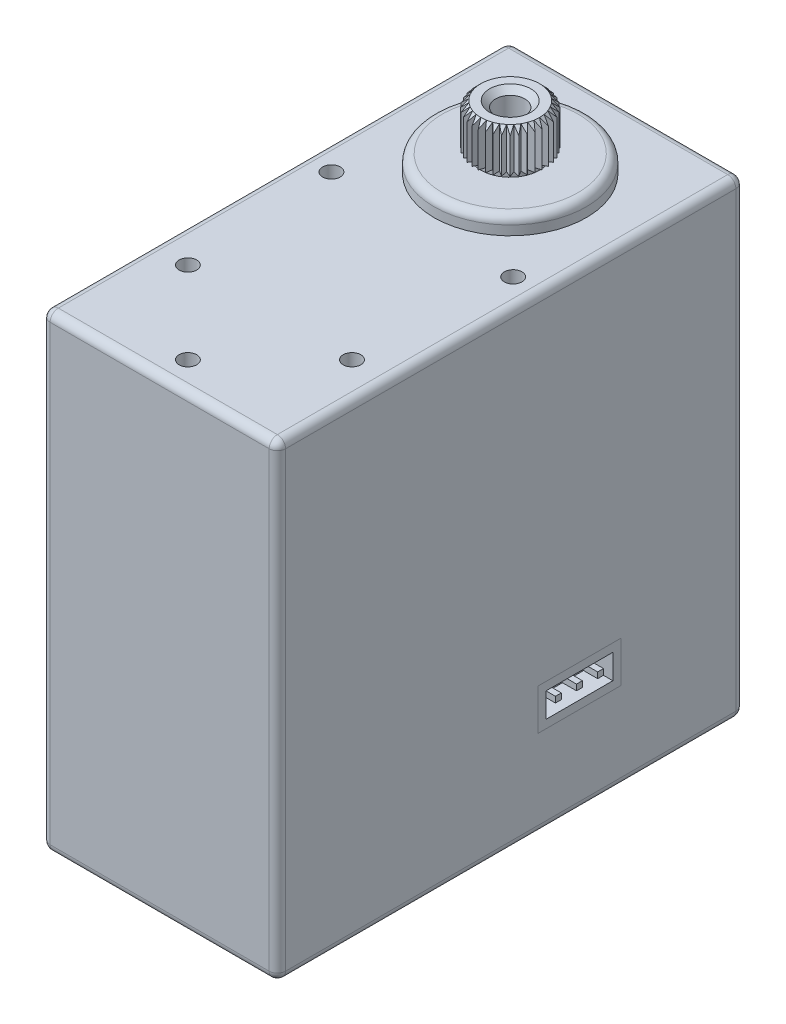
SolidWorks part; units mm, degrees
ref_plane "Alzado" through (0, 0, 0) normal (0, 0, 1) x (1, 0, 0)
ref_plane "Planta" through (0, 0, 0) normal (0, 1, 0) x (1, 0, 0)
ref_plane "Vista lateral" through (0, 0, 0) normal (1, 0, 0) x (0, 0, -1)
sketch "Croquis2" plane through (0, 0, 0) normal (0, 1, 0) x (1, 0, 0)
  line L0 (0, 0) -> (0, -27.5) construction
  line L1 (0, 7.5) -> (0, 9.91) construction
  line L2 (0, -7.5) -> (7.75, -7.5) construction
  line L3 (0, -20.5) -> (7, -20.5) construction
  line L4 (0, 0) -> (0, 7.5) construction
  line L5 (0, 7.5) -> (7.5, 7.5)
  line L6 (0, -27.5) -> (0, -29.91) construction
  line L7 (-10.045, -29.91) -> (10.045, -29.91)
  line L8 (-10.045, 9.91) -> (10.045, 9.91)
  line L9 (10.045, -29.91) -> (10.045, 9.91)
  line L10 (-10.045, -29.91) -> (-10.045, 9.91)
  circle A0 centre (0, 0) radius 3
  circle A3 centre (0, 0) radius 6.5
  circle A4 centre (7, -20.5) radius 0.75
  circle A6 centre (7.5, 7.5) radius 0.75
  circle A10 centre (0, -27.5) radius 0.75
  circle A11 centre (7.75, -7.5) radius 0.75
  circle A13 centre (-7, -20.5) radius 0.75
  circle A14 centre (-7.75, -7.5) radius 0.75
  dimension "D1" = 27.5
  dimension "D2" = 6
  dimension "D3" = 7
  dimension "D4" = 13
  dimension "D7" = 13
  dimension "D5" = 1.5
  dimension "D10" = 1.5
  dimension "D11" = 2.41
  dimension "D12" = 1.5
  dimension "D13" = 2.41
  dimension "D9" = 1.5
  dimension "D6" = 7
  dimension "D8" = 7.5
  dimension "D14" = 10.045
  dimension "D15" = 10.045
  dimension "D16" = 7.75
extrude "Saliente-Extruir1" add sketch "Croquis2" along normal blind 5.4 contours A0 region at (0, 0, 0)
extrude "Saliente-Extruir2" add sketch "Croquis2<4>" along normal blind 1.5 contours A3 region at (-6.3162, 0, 0)
sketch "Croquis2<4>" plane through (0, 0, 0) normal (0, 1, 0) x (1, 0, 0) same geometry as "Croquis2"
extrude "Saliente-Extruir3" add sketch "Croquis2<6>" against normal blind 40 separate body contours L10 L7 L9 L8 A14 A11 A10 A6 A4 A3 A13 | A10 | A4 | A13 | A11 | A14 | A6 | A3 A0 | A0 region at (-0.0202, 0, 11.9783) region at (0, 0, 0) region at (-6.3162, 0, 0) region at (7, 0, 20.5) region at (7.5, 0, -6.7712) region at (0, 0, 27.5) region at (7.75, 0, 7.5) region at (-7, 0, 20.5) region at (-7.75, 0, 7.5)
sketch "Croquis2<6>" plane through (0, 0, 0) normal (0, 1, 0) x (1, 0, 0) same geometry as "Croquis2"
extrude "Cortar-Extruir1" cut sketch "Croquis2<7>" against normal blind 2 contours A10 | A4 | A13 | A14 | A11 region at (7, 0, 20.5) region at (0, 0, 27.5) region at (7.75, 0, 7.5) region at (-7, 0, 20.5) region at (-7.75, 0, 7.5)
sketch "Croquis2<7>" plane through (0, 0, 0) normal (0, 1, 0) x (1, 0, 0) same geometry as "Croquis2"
extrude "Saliente-Extruir4" add sketch "Croquis2<8>" against normal blind 41.5 contours A3
sketch "Croquis2<8>" plane through (0, 0, 0) normal (0, 1, 0) x (1, 0, 0) same geometry as "Croquis2"
extrude "Saliente-Extruir5" add sketch "Croquis2<10>" against normal blind 45.7 contours A0
sketch "Croquis2<10>" plane through (0, 0, 0) normal (0, 1, 0) x (1, 0, 0) same geometry as "Croquis2"
sketch "Croquis3" plane through (0, -40, 0) normal (0, -1, 0) x (1, 0, 0)
  line L0 (0, 0) -> (0, 27.5) construction
  line L1 (0, 27.5) -> (-7.5, 27.5) construction
  line L2 (-7.5, -7.5) -> (-10.045, -7.5) construction
  line L3 (-10.045, 29.91) -> (-10.045, -9.91) construction
  line L4 (-7.5, -7.5) -> (-7.5, -9.91) construction
  line L5 (-10.045, -9.91) -> (10.045, -9.91) construction
  circle A0 centre (-7.5, 12.5) radius 0.75
  circle A1 centre (-7.5, -7.5) radius 0.75
  circle A2 centre (-7.5, 27.5) radius 0.75
  circle A3 centre (7.5, -7.5) radius 0.75
  circle A4 centre (7.5, 12.5) radius 0.75
  circle A5 centre (7.5, 27.5) radius 0.75
  dimension "D3" = 1.5
  dimension "D4" = 1.5
  dimension "D5" = 1.5
  dimension "D1" = 27.5
  dimension "D2" = 7.5
  dimension "D6" = 7.5
  dimension "D7" = 15
  dimension "D8" = 20
  dimension "D9" = 7.5
extrude "Cortar-Extruir2" cut sketch "Croquis3" against normal blind 2
sketch "Croquis5" plane through (0, 0, -9.91) normal (0, 0, -1) x (-1, 0, 0)
  line L0 (-10.045, -40) -> (-10.045, 0) construction
  line L1 (-3.545, -29) -> (3.545, -29)
  line L2 (-3.545, -29) -> (-3.545, -32.5)
  line L3 (-3.545, -32.5) -> (3.545, -32.5)
  line L4 (3.545, -29) -> (3.545, -32.5)
  line L5 (-6.5, -40) -> (6.5, -40) construction
  line L6 (10.045, -40) -> (10.045, 0) construction
  line L7 (-2.845, -31.8) -> (2.845, -31.8)
  line L8 (2.845, -29.7) -> (2.845, -31.8)
  line L9 (-2.845, -29.7) -> (2.845, -29.7)
  line L10 (-2.845, -29.7) -> (-2.845, -31.8)
  line L12 (-10.045, -29) -> (10.045, -29)
  line L13 (-10.045, -29) -> (-10.045, -12)
  line L14 (-10.045, -12) -> (10.045, -12)
  line L15 (10.045, -29) -> (10.045, -12)
  dimension "D1" = 6.5
  dimension "D2" = 7.5
  dimension "D3" = 6.5
  dimension "D4" = 3.5
  dimension "D5" = 17
extrude "Cortar-Extruir5" cut sketch "Croquis5" against normal blind 2 contours L9 L10 L7 L8 | L4 L1 L2 L3 L10 L9 L8 L7 region at (0, -29.0791, -9.91) region at (0, -30.75, -9.91)
extrude "Saliente-Extruir6" add sketch "Croquis5<4>" against normal blind 2 separate body contours L4 L1 L2 L3 L10 L9 L8 L7 region at (0, -29.0791, -9.91)
sketch "Croquis5<4>" plane through (0, 0, -9.91) normal (0, 0, -1) x (-1, 0, 0) same geometry as "Croquis5"
sketch "Croquis8" plane through (-10.045, 0, 0) normal (-1, 0, 0) x (0, 0, 1)
  line L0 (-9.91, -29) -> (-9.91, -12) construction
  line L1 (-9.91, -29) -> (0.59, -29)
  line L2 (-9.91, -29) -> (-9.91, -12)
  line L3 (-9.91, -12) -> (29.91, -12)
  line L4 (29.91, -29) -> (29.91, -12)
  line L5 (-9.91, -29) -> (-9.91, -32.5) construction
  line L6 (29.91, -40) -> (29.91, 0) construction
  line L7 (-9.91, -29.7) -> (-9.91, -31.8) construction
  line L9 (0.59, -29) -> (0.59, -32.5)
  line L10 (0.59, -32.5) -> (7.68, -32.5)
  line L11 (7.68, -29) -> (7.68, -32.5)
  line L12 (7.68, -29) -> (29.91, -29)
  line L13 (0.59, -29) -> (7.68, -29)
  line L14 (6.98, -29.7) -> (6.98, -31.8)
  line L15 (1.29, -31.8) -> (6.98, -31.8)
  line L16 (1.29, -29.7) -> (1.29, -31.8)
  line L17 (1.29, -29.7) -> (6.98, -29.7)
  dimension "D1" = 3.5
  dimension "D2" = 7.09
  dimension "D3" = 10.5
extrude "Cortar-Extruir6" cut sketch "Croquis8" against normal blind 2 contours L13 L9 L10 L11 L16 L17 L14 L15 | L17 L16 L15 L14 region at (-10.045, -29.0791, 4.135) region at (-10.045, -30.75, 4.135)
extrude "Saliente-Extruir9" add sketch "Croquis8<6>" against normal blind 2 separate body contours L13 L9 L10 L11 L16 L17 L14 L15 region at (-10.045, -29.0791, 4.135)
sketch "Croquis8<6>" plane through (-10.045, 0, 0) normal (-1, 0, 0) x (0, 0, 1) same geometry as "Croquis8"
mirror "Simetría1" about plane through (0, 0, 0) normal (1, 0, 0) of "Cortar-Extruir6"
mirror "Simetría4" about plane through (0, 0, 0) normal (1, 0, 0) of bodies 116
fillet "Redondeo1" radius 0.7 12 edges at (-10.045, -20, 29.91) (0, -40, 29.91) (10.045, -40, 10) (-10.045, -40, 10) (0, -40, -9.91) (0, 0, -9.91) (10.045, 0, 10) (0, 0, 29.91) (-10.045, 0, 10) (-10.045, -20, -9.91) (10.045, -20, 29.91) (10.045, -20, -9.91)
fillet "Redondeo2" radius 0.7 3 edges at (0, -41.5, 6.5) (0, -41.5, 3) (0, 1.5, 6.5)
chamfer "Chaflán1" distance 0.5 angle 45 1 edges at (0, 5.4, 3)
sketch "Croquis9" plane through (0, 5.4, 0) normal (0, 1, 0) x (1, 0, 0)
  line L0 (0, 0) -> (0, 3) construction
  line L1 (0, 0) -> (0.2615, 2.9886) construction
  line L2 (0, 2.5) -> (0.2615, 2.9886)
  line L3 (0, 2.5) -> (-0.2615, 2.9886)
  line L4 (0, 0) -> (-0.2615, 2.9886) construction
  line L5 (0.4341, 2.462) -> (0.7765, 2.8978)
  line L6 (0.4341, 2.462) -> (0.2615, 2.9886)
  line L7 (0.8551, 2.3492) -> (1.2679, 2.7189)
  line L8 (0.8551, 2.3492) -> (0.7765, 2.8978)
  line L9 (1.25, 2.1651) -> (1.7207, 2.4575)
  line L10 (1.25, 2.1651) -> (1.2679, 2.7189)
  line L11 (1.607, 1.9151) -> (2.1213, 2.1213)
  line L12 (1.607, 1.9151) -> (1.7207, 2.4575)
  line L13 (1.9151, 1.607) -> (2.4575, 1.7207)
  line L14 (1.9151, 1.607) -> (2.1213, 2.1213)
  line L15 (2.1651, 1.25) -> (2.7189, 1.2679)
  line L16 (2.1651, 1.25) -> (2.4575, 1.7207)
  line L17 (2.3492, 0.8551) -> (2.8978, 0.7765)
  line L18 (2.3492, 0.8551) -> (2.7189, 1.2679)
  line L19 (2.462, 0.4341) -> (2.9886, 0.2615)
  line L20 (2.462, 0.4341) -> (2.8978, 0.7765)
  line L21 (2.5, 0) -> (2.9886, -0.2615)
  line L22 (2.5, 0) -> (2.9886, 0.2615)
  line L23 (2.462, -0.4341) -> (2.8978, -0.7765)
  line L24 (2.462, -0.4341) -> (2.9886, -0.2615)
  line L25 (2.3492, -0.8551) -> (2.7189, -1.2679)
  line L26 (2.3492, -0.8551) -> (2.8978, -0.7765)
  line L27 (2.1651, -1.25) -> (2.4575, -1.7207)
  line L28 (2.1651, -1.25) -> (2.7189, -1.2679)
  line L29 (1.9151, -1.607) -> (2.1213, -2.1213)
  line L30 (1.9151, -1.607) -> (2.4575, -1.7207)
  line L31 (1.607, -1.9151) -> (1.7207, -2.4575)
  line L32 (1.607, -1.9151) -> (2.1213, -2.1213)
  line L33 (1.25, -2.1651) -> (1.2679, -2.7189)
  line L34 (1.25, -2.1651) -> (1.7207, -2.4575)
  line L35 (0.8551, -2.3492) -> (0.7765, -2.8978)
  line L36 (0.8551, -2.3492) -> (1.2679, -2.7189)
  line L37 (0.4341, -2.462) -> (0.2615, -2.9886)
  line L38 (0.4341, -2.462) -> (0.7765, -2.8978)
  line L39 (0, -2.5) -> (-0.2615, -2.9886)
  line L40 (0, -2.5) -> (0.2615, -2.9886)
  line L41 (-0.4341, -2.462) -> (-0.7765, -2.8978)
  line L42 (-0.4341, -2.462) -> (-0.2615, -2.9886)
  line L43 (-0.8551, -2.3492) -> (-1.2679, -2.7189)
  line L44 (-0.8551, -2.3492) -> (-0.7765, -2.8978)
  line L45 (-1.25, -2.1651) -> (-1.7207, -2.4575)
  line L46 (-1.25, -2.1651) -> (-1.2679, -2.7189)
  line L47 (-1.607, -1.9151) -> (-2.1213, -2.1213)
  line L48 (-1.607, -1.9151) -> (-1.7207, -2.4575)
  line L49 (-1.9151, -1.607) -> (-2.4575, -1.7207)
  line L50 (-1.9151, -1.607) -> (-2.1213, -2.1213)
  line L51 (-2.1651, -1.25) -> (-2.7189, -1.2679)
  line L52 (-2.1651, -1.25) -> (-2.4575, -1.7207)
  line L53 (-2.3492, -0.8551) -> (-2.8978, -0.7765)
  line L54 (-2.3492, -0.8551) -> (-2.7189, -1.2679)
  line L55 (-2.462, -0.4341) -> (-2.9886, -0.2615)
  line L56 (-2.462, -0.4341) -> (-2.8978, -0.7765)
  line L57 (-2.5, 0) -> (-2.9886, 0.2615)
  line L58 (-2.5, 0) -> (-2.9886, -0.2615)
  line L59 (-2.462, 0.4341) -> (-2.8978, 0.7765)
  line L60 (-2.462, 0.4341) -> (-2.9886, 0.2615)
  line L61 (-2.3492, 0.8551) -> (-2.7189, 1.2679)
  line L62 (-2.3492, 0.8551) -> (-2.8978, 0.7765)
  line L63 (-2.1651, 1.25) -> (-2.4575, 1.7207)
  line L64 (-2.1651, 1.25) -> (-2.7189, 1.2679)
  line L65 (-1.9151, 1.607) -> (-2.1213, 2.1213)
  line L66 (-1.9151, 1.607) -> (-2.4575, 1.7207)
  line L67 (-1.607, 1.9151) -> (-1.7207, 2.4575)
  line L68 (-1.607, 1.9151) -> (-2.1213, 2.1213)
  line L69 (-1.25, 2.1651) -> (-1.2679, 2.7189)
  line L70 (-1.25, 2.1651) -> (-1.7207, 2.4575)
  line L71 (-0.8551, 2.3492) -> (-0.7765, 2.8978)
  line L72 (-0.8551, 2.3492) -> (-1.2679, 2.7189)
  line L73 (-0.4341, 2.462) -> (-0.2615, 2.9886)
  line L74 (-0.4341, 2.462) -> (-0.7765, 2.8978)
  circle A0 centre (0, 0) radius 3 construction
  circle A2 centre (0, 0) radius 2.2 construction
  circle A4 centre (0, 0) radius 3 construction
  circle A5 centre (0, 0) radius 2.5
  circle A7 centre (0, 0) radius 5.8
  point P11 (0, 0)
  point P120 (0, 0)
  point P124 (0, 0)
  dimension "D1" = 4.4
  dimension "D2" = 5
  dimension "D3" = 36
extrude "Cortar-Extruir13" cut sketch "Croquis9" against normal blind 3.5 contours A7 L74 L73 L3 L2 L6 L5 L8 L7 L10 L9 L12 L11 L14 L13 L16 L15 L18 L17 L20 L19 L22 L21 L24 L23 L26 L25 L28 L27 L30 L29 L32 L31 L34 L33 L36 L35 L38 L37 L40 L39 L42 L41 L44 L43 L46 L45 L48 L47 L50 region at (-5.636, 5.4, 0)
sketch "Croquis10" plane through (0, 1.9, 0) normal (0, 1, 0) x (1, 0, 0)
  circle A0 centre (0, 0) radius 3
  circle A1 centre (0, 0) radius 2.5
extrude "Cortar-Extruir15" cut sketch "Croquis10" against normal up to surface (0.4 mm away) up to face at (0, 1.5, 5.8)
sketch "Croquis11" plane through (0, 5.4, 0) normal (0, 1, 0) x (1, 0, 0)
  circle A0 centre (0, 0) radius 1.25
  dimension "D1" = 2.5
extrude "Cortar-Extruir16" cut sketch "Croquis11" against normal blind 4
chamfer "Chaflán2" distance 0.5 angle 45 1 edges at (0, 5.4, 1.25)
sketch "Croquis12" plane through (8.045, 0, 0) normal (1, 0, 0) x (0, 0, -1)
  line L0 (-1.29, -30.75) -> (-6.98, -30.75) construction
  line L1 (-1.29, -29.7) -> (-1.29, -31.8) construction
  line L2 (-6.98, -29.7) -> (-6.98, -31.8) construction
  line L3 (-4.135, -30.75) -> (-4.135, -31.8) construction
  line L4 (-2.085, -30.5) -> (-2.585, -30.5)
  line L5 (-2.085, -30.5) -> (-2.085, -31)
  line L6 (-2.085, -31) -> (-2.585, -31)
  line L7 (-2.585, -30.5) -> (-2.585, -31)
  line L8 (-2.085, -30.5) -> (-2.585, -31) construction
  line L9 (-2.085, -31) -> (-2.585, -30.5) construction
  line L10 (-3.885, -30.5) -> (-4.385, -30.5)
  line L11 (-3.885, -30.5) -> (-3.885, -31)
  line L12 (-3.885, -31) -> (-4.385, -31)
  line L13 (-4.385, -30.5) -> (-4.385, -31)
  line L14 (-3.885, -30.5) -> (-4.385, -31) construction
  line L15 (-3.885, -31) -> (-4.385, -30.5) construction
  line L16 (-1.29, -31.8) -> (-6.98, -31.8) construction
  line L17 (-6.185, -31) -> (-5.685, -31)
  line L18 (-6.185, -30.5) -> (-6.185, -31)
  line L19 (-6.185, -30.5) -> (-5.685, -30.5)
  line L20 (-5.685, -30.5) -> (-5.685, -31)
  point P6 (-2.335, -30.75)
  point P11 (-4.135, -30.75)
  dimension "D1" = 1.8
  dimension "D2" = 0.5
  dimension "D3" = 0.5
  dimension "D4" = 0.5
  dimension "D5" = 0.5
extrude "Saliente-Extruir13" add sketch "Croquis12" along normal blind 2 separate body
mirror "Simetría5" about plane through (0, 0, 0) normal (1, 0, 0) of "Saliente-Extruir13"
sketch "Croquis13" plane through (0, 0, -7.91) normal (0, 0, -1) x (-1, 0, 0)
  line L0 (-2.845, -30.75) -> (2.845, -30.75) construction
  line L1 (-2.845, -29.7) -> (-2.845, -31.8) construction
  line L2 (2.845, -29.7) -> (2.845, -31.8) construction
  line L3 (0, -29.7) -> (0, -31.8) construction
  line L4 (-2.845, -29.7) -> (2.845, -29.7) construction
  line L5 (-2.845, -31.8) -> (2.845, -31.8) construction
  line L6 (-1.55, -31) -> (-2.05, -31)
  line L7 (-0.25, -31) -> (0.25, -31)
  line L8 (-0.25, -31) -> (-0.25, -30.5)
  line L9 (-0.25, -30.5) -> (0.25, -30.5)
  line L10 (0.25, -31) -> (0.25, -30.5)
  line L11 (-0.25, -31) -> (0.25, -30.5) construction
  line L12 (-0.25, -30.5) -> (0.25, -31) construction
  line L13 (1.55, -31) -> (2.05, -31)
  line L14 (1.55, -31) -> (1.55, -30.5)
  line L15 (1.55, -30.5) -> (2.05, -30.5)
  line L16 (2.05, -31) -> (2.05, -30.5)
  line L17 (1.55, -31) -> (2.05, -30.5) construction
  line L18 (1.55, -30.5) -> (2.05, -31) construction
  line L19 (-2.05, -31) -> (-2.05, -30.5)
  line L20 (-1.55, -30.5) -> (-2.05, -30.5)
  line L21 (-1.55, -31) -> (-1.55, -30.5)
  point P12 (0, -30.75)
  point P17 (1.8, -30.75)
  dimension "D1" = 0.5
  dimension "D2" = 0.5
  dimension "D3" = 0.5
  dimension "D4" = 0.5
  dimension "D5" = 1.8
extrude "Saliente-Extruir14" add sketch "Croquis13" along normal blind 2 separate body
